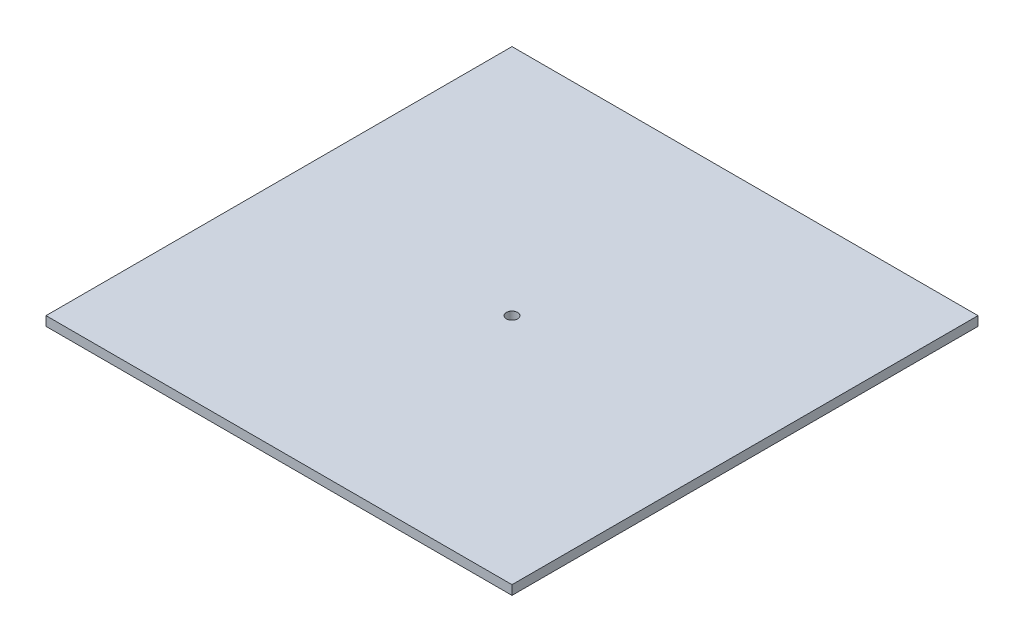
SolidWorks part; units mm, degrees
ref_plane "Plan de face" through (0, 0, 0) normal (0, 0, 1) x (1, 0, 0)
ref_plane "Plan de dessus" through (0, 0, 0) normal (0, 1, 0) x (1, 0, 0)
ref_plane "Plan de droite" through (0, 0, 0) normal (1, 0, 0) x (0, 0, -1)
sketch "Esquisse1" plane through (0, 0, 0) normal (0, 1, 0) x (1, 0, 0)
  line L1 (-250, -250) -> (250, -250)
  line L2 (-250, -250) -> (-250, 250)
  line L3 (-250, 250) -> (250, 250)
  line L4 (250, -250) -> (250, 250)
  line L5 (-250, -250) -> (250, 250) construction
  line L6 (-250, 250) -> (250, -250) construction
  point P0 (0, 0)
  dimension "D1" = 500
  dimension "D2" = 500
extrude "Boss.-Extru.1" add sketch "Esquisse1" along normal mid plane 10
sketch "Esquisse5" plane through (0, 5, 0) normal (0, 1, 0) x (1, 0, 0)
  point P0 (0, 0)
hole_wizard "Dégagement M101" positions "Esquisse5" profile "Esquisse4" hole size "M10" standard "ISO" end condition through all
sketch "Esquisse4" plane through (0, 5, 0) normal (1, 0, 0) x (0, 0, 1)
  line L0 (0, 0) -> (0, 10)
  line L1 (0, 10) -> (6, 10)
  line L2 (6, 10) -> (6, 0.025)
  line L3 (6, 0.025) -> (6.025, 0)
  line L5 (6.025, 0) -> (0, 0)
  line L6 (-6, 0.025) -> (-6.025, 0) construction
  line L11 (0, -6.35) -> (0, 107.95) construction
  dimension "Diamètre du perçage jusqu'au prochain" = 12
  dimension "Profondeur du perçage jusqu'au prochain" = 10
  dimension "Diamètre du fraisage entrant" = 12.05
  dimension "Angle du fraisage entrant" = 90
